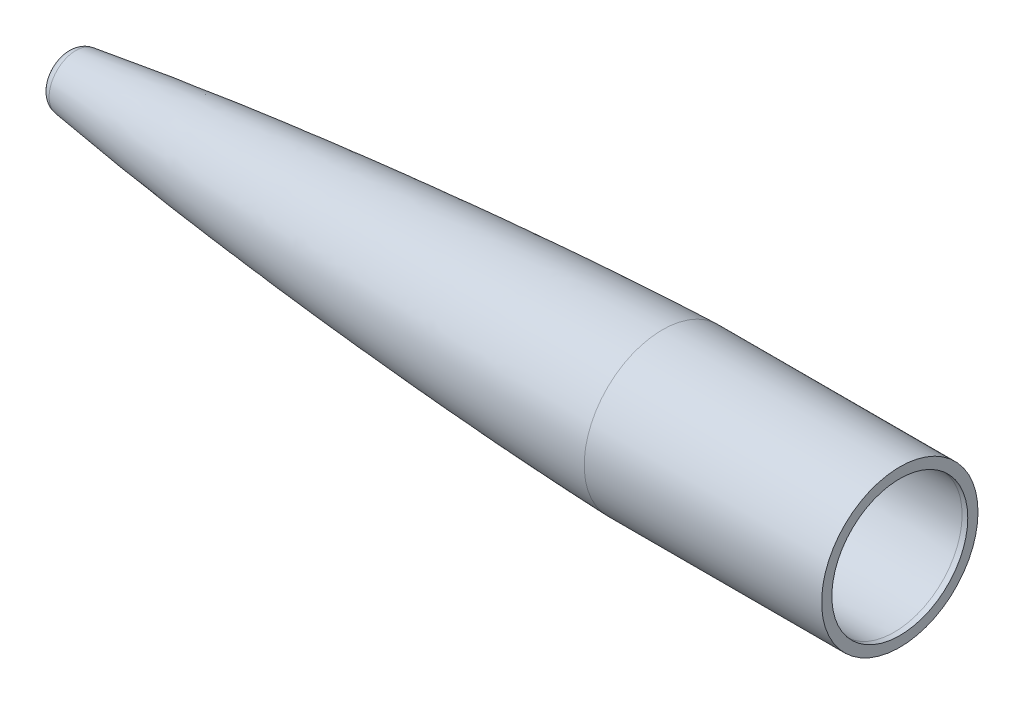
SolidWorks part; units mm, degrees
ref_plane "Front Plane" through (0, 0, 0) normal (0, 0, 1) x (1, 0, 0)
ref_plane "Top Plane" through (0, 0, 0) normal (0, 1, 0) x (1, 0, 0)
ref_plane "Right Plane" through (0, 0, 0) normal (1, 0, 0) x (0, 0, -1)
sketch "Sketch1" plane through (0, 0, 0) normal (0, 0, 1) x (1, 0, 0)
  line L2 (0, -76.2) -> (-921.7152, -76.2) construction
  line L3 (6.35, 6.35) -> (6.35, 0)
  line L4 (-259.8125, 11.4606) -> (6.35, 11.4606)
  line L5 (0, 0) -> (6.35, 0)
  line L6 (6.35, 6.35) -> (6.35, -76.2) construction
  line L7 (0, 0) -> (0, -76.2) construction
  line L8 (-921.7152, -58.5997) -> (-928.0652, -58.5997)
  line L9 (-928.0652, -58.5997) -> (-928.0652, -76.2) construction
  line L10 (-921.7152, -58.5997) -> (-921.7152, -76.2) construction
  line L11 (6.35, 11.4606) -> (6.35, 6.35)
  arc A0 (-254, 2.1118) -> (-248.4137, -0.891) centre (-248.6021, 5.4563) ccw
  arc A2 (-916.3053, -52.3197) -> (-921.7152, -58.5997) centre (-915.3652, -58.5997) ccw
  arc A4 (-254, 2.1118) -> (-259.6052, 5.114) centre (-259.3979, -1.2327) ccw
  arc A6 (-248.6021, 5.4563) -> (-248.6021, 5.4563) centre (-248.6021, 5.4563) ccw
  arc A7 (-248.6021, 5.4563) -> (-259.8125, 11.4606) centre (-259.3979, -1.2327) ccw
  arc A8 (-917.2454, -46.0396) -> (-928.0652, -58.5997) centre (-915.3652, -58.5997) ccw
  spline S0 degree 3 poles (0, 0) (-50.8, 0) (-101.6, 0) (-157.1824, 0) (-166.7471, 0) (-181.0943, 0) (-190.659, 0) (-199.5851, 0) (-207.8726, 0) (-220.3048, -0.155) (-228.5897, -0.3615) (-235.0947, -0.5237) (-239.8196, -0.6415) (-245.0466, -0.7915) (-247.9113, -0.876) (-248.4137, -0.891) knots 0.761574 0.761574 0.761574 0.761574 0.907842 0.907842 0.921611 0.935381 0.949151 0.949151 0.961082 0.973013 0.984944 0.984944 0.991748 0.998553 1 1 1 1
  spline S1 degree 1 poles (6.35, 6.35) (-248.6021, 5.4563) knots 0 0 1 1 construction
  spline S2 degree 3 poles (-259.6052, 5.114) (-267.1277, 4.8682) (-283.426, 4.2857) (-317.2703, 2.8805) (-361.13, 0.7112) (-431.2755, -3.372) (-501.3729, -8.2669) (-571.4145, -13.8917) (-623.9147, -18.4777) (-676.3803, -23.4393) (-728.8057, -28.7991) (-772.4536, -33.6275) (-807.3418, -37.7392) (-833.4907, -40.9589) (-859.6194, -44.3289) (-885.7239, -47.8693) (-904.6125, -50.5779) (-914.801, -52.0945) (-916.3053, -52.3197) knots 0.121539 0.121539 0.121539 0.121539 0.143123 0.168303 0.218664 0.269025 0.369746 0.420107 0.470467 0.520828 0.571189 0.62155 0.64673 0.67191 0.697091 0.722271 0.747451 0.751814 0.751814 0.751814 0.751814
  spline S3 degree 1 poles (-259.8125, 11.4606) (-917.2454, -46.0396) knots 0 0 1 1 construction
  spline S4 degree 3 poles (6.35, 6.35) (-14.881, 6.35) (-57.3424, 6.3506) (-110.4226, 6.3484) (-152.8795, 6.3528) (-179.4314, 6.3414) (-200.6356, 6.3648) (-216.6826, 6.282) (-232.6614, 5.8947) (-243.2867, 5.614) (-248.6021, 5.4563) knots 0.75548 0.75548 0.75548 0.75548 0.81661 0.87774 0.908305 0.93887 0.954152 0.969435 0.984717 1 1 1 1
  spline S5 degree 3 poles (-259.8125, 11.4606) (-287.3121, 10.5623) (-342.298, 8.1716) (-452.1401, 1.8335) (-589.2803, -8.5121) (-726.1766, -21.7709) (-835.4658, -34.5887) (-890.027, -41.9652) (-917.2454, -46.0396) knots 0.121539 0.121539 0.121539 0.121539 0.200324 0.279108 0.436676 0.594245 0.673029 0.751814 0.751814 0.751814 0.751814
revolve "Revolve1" add sketch "Sketch1" angle 360 about L2 region at (-124.3289, 8.8839, 0) region at (-3.0204, 3.175, 0)
